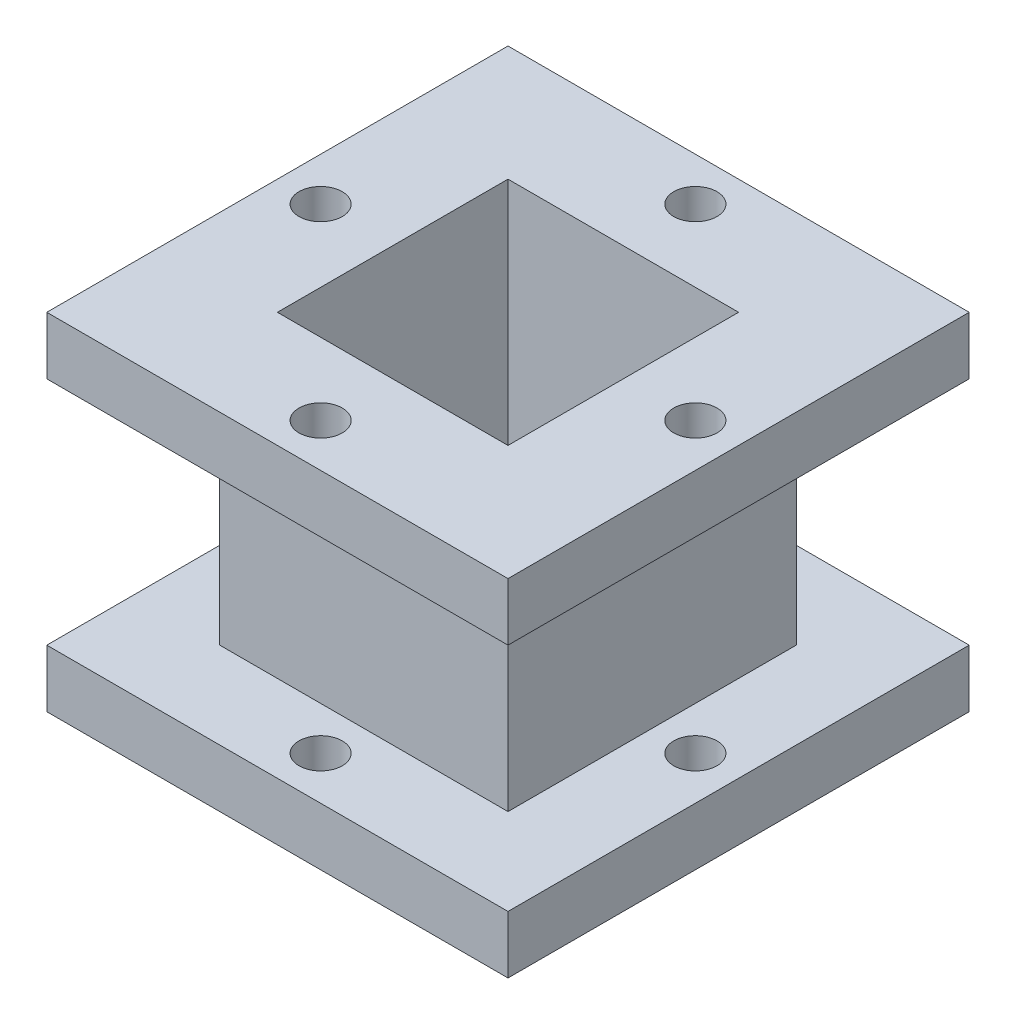
SolidWorks part; units mm, degrees
other "Markup1"
sketch "Sketch6" plane through (-25.4, 38.1, 25.4) normal (-0.2494, 0.4996, 0.8296) x (0.9666, 0.0765, 0.2445)
material "PVAL"
ref_plane "Front Plane" through (0, 0, 0) normal (0, 0, 1) x (1, 0, 0)
ref_plane "Top Plane" through (0, 0, 0) normal (0, 1, 0) x (1, 0, 0)
ref_plane "Right Plane" through (0, 0, 0) normal (1, 0, 0) x (0, 0, -1)
sketch "Sketch1" plane through (0, 0, 0) normal (0, 1, 0) x (1, 0, 0)
  line L1 (-25.4, -25.4) -> (25.4, -25.4)
  line L2 (-25.4, -25.4) -> (-25.4, 25.4)
  line L3 (-25.4, 25.4) -> (25.4, 25.4)
  line L4 (25.4, -25.4) -> (25.4, 25.4)
  line L5 (-25.4, -25.4) -> (25.4, 25.4) construction
  line L6 (-25.4, 25.4) -> (25.4, -25.4) construction
  point P0 (0, 0)
  dimension "D1" = 50.8
  dimension "D2" = 50.8
extrude "Boss-Extrude1" add sketch "Sketch1" along normal blind 6.35
sketch "Sketch2" plane through (0, 6.35, 0) normal (0, 1, 0) x (1, 0, 0)
  line L0 (25.4, 25.4) -> (-25.4, 25.4) construction
  line L1 (-15.875, -15.875) -> (15.875, -15.875)
  line L2 (-15.875, -15.875) -> (-15.875, 15.875)
  line L3 (-15.875, 15.875) -> (15.875, 15.875)
  line L4 (15.875, -15.875) -> (15.875, 15.875)
  line L5 (-15.875, -15.875) -> (15.875, 15.875) construction
  line L6 (-15.875, 15.875) -> (15.875, -15.875) construction
  line L7 (25.4, -25.4) -> (25.4, 25.4) construction
  point P0 (0, 0)
  dimension "D1" = 9.525
  dimension "D2" = 9.525
extrude "Boss-Extrude2" add sketch "Sketch2" along normal blind 25.4 contours L2 L1 L4 L3
sketch "Sketch3" plane through (0, 31.75, 0) normal (0, 1, 0) x (1, 0, 0)
  line L0 (25.4, 25.4) -> (-25.4, 25.4) construction
  line L1 (-25.4, -25.4) -> (25.4, -25.4)
  line L2 (-25.4, -25.4) -> (-25.4, 25.4)
  line L3 (-25.4, 25.4) -> (25.4, 25.4)
  line L4 (25.4, -25.4) -> (25.4, 25.4)
  line L5 (-25.4, -25.4) -> (25.4, 25.4) construction
  line L6 (-25.4, 25.4) -> (25.4, -25.4) construction
  line L7 (25.4, -25.4) -> (25.4, 25.4) construction
  point P0 (0, 0)
  dimension "D1" = 0
  dimension "D2" = 0
extrude "Boss-Extrude3" add sketch "Sketch3" along normal blind 6.35
sketch "Sketch4" plane through (0, 38.1, 0) normal (0, 1, 0) x (1, 0, 0)
  line L1 (-12.7, -12.7) -> (12.7, -12.7)
  line L2 (-12.7, -12.7) -> (-12.7, 12.7)
  line L3 (-12.7, 12.7) -> (12.7, 12.7)
  line L4 (12.7, -12.7) -> (12.7, 12.7)
  line L5 (-12.7, -12.7) -> (12.7, 12.7) construction
  line L6 (-12.7, 12.7) -> (12.7, -12.7) construction
  point P0 (0, 0)
  dimension "D1" = 25.4
  dimension "D2" = 25.4
extrude "Cut-Extrude1" cut sketch "Sketch4" against normal through all
ref_plane "Plane2" through (0, 0, 0) normal (-1, 0, 0) x (0, 0, 1)
ref_axis "Axis2" through (0, 38.1, -36.3412) along (0, 0, 1)
ref_plane "Plane3" through (0, 0, 0) normal (0, 0, 1) x (1, 0, 0)
ref_axis "Axis3" through (-12.7, 38.1, 0) along (1, 0, 0)
ref_plane "Plane4" through (0, 38.1, 0) normal (0, 1, 0) x (1, 0, 0)
ref_axis "Axis4" through (0, -6.9083, 0) along (0, 1, 0)
ref_plane "Plane5" through (0, 0, 20.6375) normal (0, 0, 1) x (1, 0, 0)
ref_axis "Axis5" through (-25.4, 38.1, 20.6375) along (1, 0, 0)
ref_point "Point1"
sketch "Sketch5" plane through (0, 38.1, 0) normal (0, 1, 0) x (1, 0, 0)
  circle A0 centre (0, -20.6375) radius 2.3813
  dimension "D1" = 4.7625
extrude "Cut-Extrude2" cut sketch "Sketch5" against normal through all contours A0
pattern_circular "CirPattern1" count 4 over 360 about axis through (0, -6.9083, 0) along (0, 1, 0) of "Cut-Extrude2"
scale "Scale1" bodies to scale 110 scale about centroid uniform scaling yes scale factor 1.02
